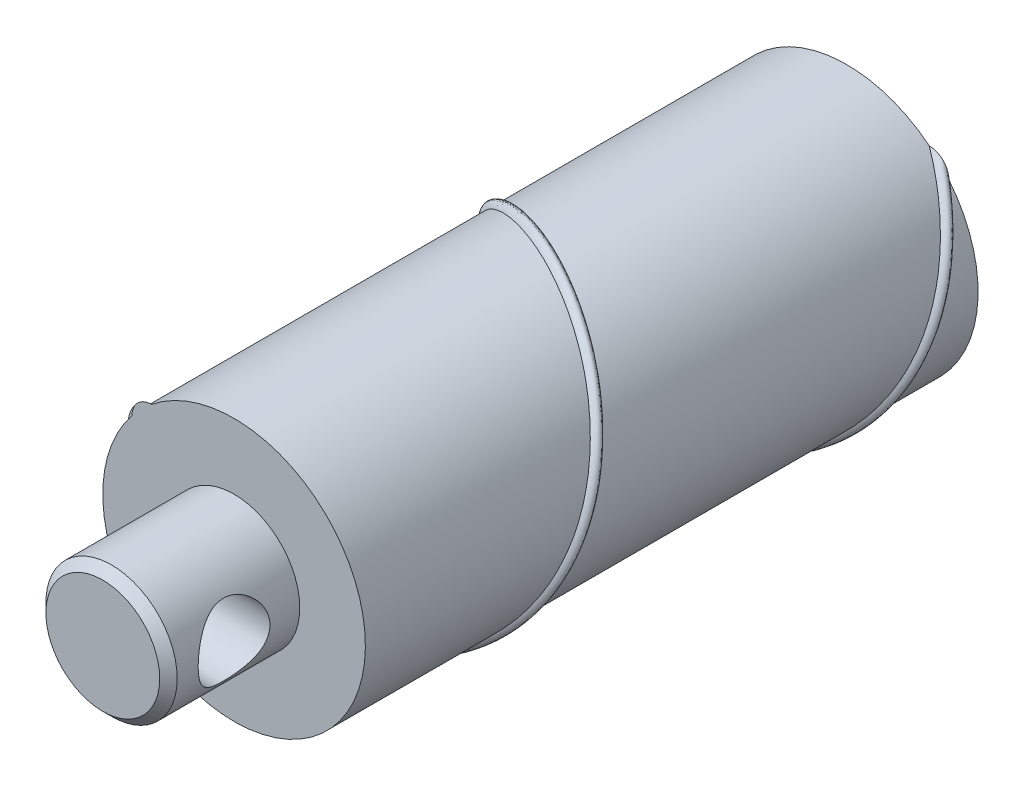
SolidWorks part; units mm, degrees
ref_plane "정면" through (0, 0, 0) normal (0, 0, 1) x (1, 0, 0)
ref_plane "윗면" through (0, 0, 0) normal (0, 1, 0) x (1, 0, 0)
ref_plane "우측면" through (0, 0, 0) normal (1, 0, 0) x (0, 0, -1)
sketch "스케치1" plane through (0, 0, 0) normal (0, 0, 1) x (1, 0, 0)
  circle A0 centre (0, 0) radius 9.05
  circle A1 centre (0, 0) radius 15
  circle A2 centre (0, 0) radius 12.05
  dimension "D1" = 18.1
  dimension "D2" = 30
  dimension "D3" = 24.1
extrude "보스-돌출1" add sketch "스케치1" along normal blind 250 contours A1
sketch "스케치2" plane through (0, 0, 0) normal (0, 0, 1) x (1, 0, 0)
  circle A0 centre (0, 0) radius 13.3228
curve "나선형 곡선1" pitch 40 height 250 radius 13.3228 left hand yes centre (0, 0, 0) axis (0, 0, 1) start towards (1, 0, 0)
sketch "스케치5" plane through (0, 0, 0) normal (0, 0, 1) x (1, 0, 0)
  circle A0 centre (-9.4206, -9.4206) radius 2.25
  dimension "D1" = 4.5
sweep "스윕1" add profiles "스케치5" path "나선형 곡선1"
extrude "컷-돌출1" cut sketch "스케치1<3>" along normal blind 105 contours A0 region at (0, 0, 0)
sketch "스케치1<3>" plane through (0, 0, 0) normal (0, 0, 1) x (1, 0, 0) same geometry as "스케치1"
extrude "컷-돌출2" cut sketch "스케치1<4>" along normal blind 4.3 contours A2
sketch "스케치1<4>" plane through (0, 0, 0) normal (0, 0, 1) x (1, 0, 0) same geometry as "스케치1"
sketch "스케치6" plane through (0, 0, 250) normal (0, 0, 1) x (1, 0, 0)
  circle A0 centre (0, 0) radius 7.5
  dimension "D1" = 15
extrude "보스-돌출2" add sketch "스케치6" along normal blind 15
sketch "스케치7" plane through (0, 0, 105) normal (0, 0, -1) x (-1, 0, 0)
  circle A0 centre (0, 0) radius 3.1
  dimension "D1" = 6.2
extrude "컷-돌출3" cut sketch "스케치7" against normal blind 131
chamfer "모따기1" distance 1 angle 45 1 edges at (-3.1, 0, 105)
sketch "스케치8" plane through (0, 0, 0) normal (0, 1, 0) x (1, 0, 0)
  circle A0 centre (0, -19) radius 4.1
  circle A1 centre (0, -49) radius 4.1
  dimension "D1" = 8.2
  dimension "D2" = 8.2
  dimension "D3" = 30
  dimension "D4" = 19
extrude "컷-돌출4" cut sketch "스케치8" against normal through all both and the other way through all
sketch "스케치9" plane through (0, 0, 0) normal (1, 0, 0) x (0, 0, -1)
  line L0 (-265, 7.5) -> (-265, -7.5) construction
  circle A0 centre (-257.5, 0) radius 4.1
  dimension "D1" = 7.5
  dimension "D2" = 8.2
extrude "컷-돌출5" cut sketch "스케치9" against normal through all both and the other way through all
chamfer "모따기2" distance 1 angle 45 1 edges at (7.5, 0, 265)
ref_plane "평면1" through (0, 0, 180) normal (0, 0, 1) x (1, 0, 0)
sketch "스케치10" plane through (0, 0, 180) normal (0, 0, 1) x (1, 0, 0)
  line L1 (-51.4585, 36.4039) -> (51.4585, 36.4039)
  line L2 (-51.4585, 36.4039) -> (-51.4585, -36.4039)
  line L3 (-51.4585, -36.4039) -> (51.4585, -36.4039)
  line L4 (51.4585, 36.4039) -> (51.4585, -36.4039)
  line L5 (-51.4585, 36.4039) -> (51.4585, -36.4039) construction
  line L6 (-51.4585, -36.4039) -> (51.4585, 36.4039) construction
  point P0 (0, 0)
extrude "컷-돌출6" cut sketch "스케치10" against normal through all contours L3 L4 L1 L2
sketch "스케치11" plane through (0, 0, 0) normal (1, 0, 0) x (0, 0, -1)
  line L0 (-180, 23.3051) -> (-180, -23.3051) construction
  line L1 (-190.1, 10.05) -> (-180, 10.05)
  line L2 (-190.1, 10.05) -> (-190.1, -10.05)
  line L3 (-190.1, -10.05) -> (-180, -10.05)
  line L4 (-180, 10.05) -> (-180, -10.05)
  line L5 (-190.1, 10.05) -> (-180, -10.05) construction
  line L6 (-190.1, -10.05) -> (-180, 10.05) construction
  line L7 (-257.5, 0) -> (-134.7388, 0) construction
  point P0 (-185.05, 0)
  dimension "D1" = 10.1
  dimension "D2" = 20.1
extrude "컷-돌출7" cut sketch "스케치11" against normal mid plane 10.1
